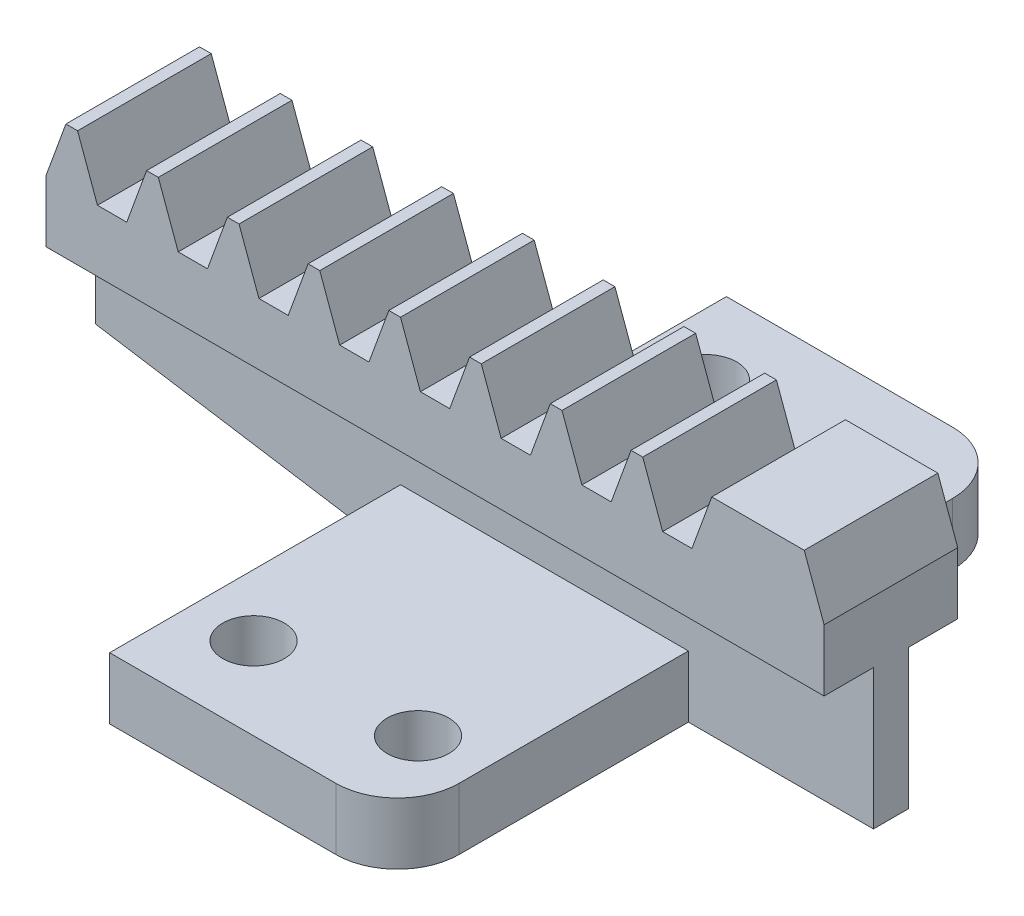
SolidWorks part; units mm, degrees
material "ABS"
ref_plane "Plan de face" through (0, 0, 0) normal (0, 0, 1) x (1, 0, 0)
ref_plane "Plan de dessus" through (0, 0, 0) normal (0, 1, 0) x (1, 0, 0)
ref_plane "Plan de droite" through (0, 0, 0) normal (1, 0, 0) x (0, 0, -1)
sketch "Esquisse1" plane through (0, 0, 0) normal (0, 0, 1) x (1, 0, 0)
  circle A1 centre (0, 0) radius 2.5
  arc A192 (-2.7975, 7.3493) -> (-3.2186, 7.1749) centre (0, 0) ccw
  arc A193 (-3.7466, 7.3576) -> (-3.2186, 7.1749) centre (-3.3855, 7.5469) ccw
  arc A194 (-3.7466, 7.3576) -> (-5.4988, 8.9274) centre (-6.7243, 5.7967) ccw
  arc A195 (-5.4988, 8.9274) -> (-6.1435, 8.4966) centre (0, 0) ccw
  arc A196 (-6.1435, 8.4966) -> (-5.3638, 6.2771) centre (-2.7822, 8.4307) ccw
  arc A197 (-5.397, 5.7193) -> (-5.3638, 6.2771) centre (-5.6769, 6.0159) ccw
  arc A198 (-5.397, 5.7193) -> (-5.7193, 5.397) centre (0, 0) ccw
  arc A199 (-6.2771, 5.3638) -> (-5.7193, 5.397) centre (-6.0159, 5.6769) ccw
  arc A200 (-6.2771, 5.3638) -> (-8.4966, 6.1435) centre (-8.4307, 2.7822) ccw
  arc A201 (-8.4966, 6.1435) -> (-8.9274, 5.4988) centre (0, 0) ccw
  arc A202 (-8.9274, 5.4988) -> (-7.3576, 3.7466) centre (-5.7967, 6.7243) ccw
  arc A203 (-7.1749, 3.2186) -> (-7.3576, 3.7466) centre (-7.5469, 3.3855) ccw
  arc A204 (-7.1749, 3.2186) -> (-7.3493, 2.7975) centre (0, 0) ccw
  arc A205 (-7.8519, 2.5534) -> (-7.3493, 2.7975) centre (-7.7304, 2.9426) ccw
  arc A206 (-7.8519, 2.5534) -> (-10.2009, 2.4244) centre (-8.8537, -0.6559) ccw
  arc A207 (-10.2009, 2.4244) -> (-10.3521, 1.6639) centre (0, 0) ccw
  arc A208 (-10.3521, 1.6639) -> (-8.2313, 0.6458) centre (-7.9287, 3.9941) ccw
  arc A209 (-7.8604, 0.2279) -> (-8.2313, 0.6458) centre (-8.268, 0.2397) ccw
  arc A210 (-7.8604, 0.2279) -> (-7.8604, -0.2279) centre (0, 0) ccw
  arc A211 (-8.2313, -0.6458) -> (-7.8604, -0.2279) centre (-8.268, -0.2397) ccw
  arc A212 (-8.2313, -0.6458) -> (-10.3521, -1.6639) centre (-7.9287, -3.9941) ccw
  arc A213 (-10.3521, -1.6639) -> (-10.2009, -2.4244) centre (0, 0) ccw
  arc A214 (-10.2009, -2.4244) -> (-7.8519, -2.5534) centre (-8.8537, 0.6559) ccw
  arc A215 (-7.3493, -2.7975) -> (-7.8519, -2.5534) centre (-7.7304, -2.9426) ccw
  arc A216 (-7.3493, -2.7975) -> (-7.1749, -3.2186) centre (0, 0) ccw
  arc A217 (-7.3576, -3.7466) -> (-7.1749, -3.2186) centre (-7.5469, -3.3855) ccw
  arc A218 (-7.3576, -3.7466) -> (-8.9274, -5.4988) centre (-5.7967, -6.7243) ccw
  arc A219 (-8.9274, -5.4988) -> (-8.4966, -6.1435) centre (0, 0) ccw
  arc A220 (-8.4966, -6.1435) -> (-6.2771, -5.3638) centre (-8.4307, -2.7822) ccw
  arc A221 (-5.7193, -5.397) -> (-6.2771, -5.3638) centre (-6.0159, -5.6769) ccw
  arc A222 (-5.7193, -5.397) -> (-5.397, -5.7193) centre (0, 0) ccw
  arc A223 (-5.3638, -6.2771) -> (-5.397, -5.7193) centre (-5.6769, -6.0159) ccw
  arc A224 (-5.3638, -6.2771) -> (-6.1435, -8.4966) centre (-2.7822, -8.4307) ccw
  arc A225 (-6.1435, -8.4966) -> (-5.4988, -8.9274) centre (0, 0) ccw
  arc A226 (-5.4988, -8.9274) -> (-3.7466, -7.3576) centre (-6.7243, -5.7967) ccw
  arc A227 (-3.2186, -7.1749) -> (-3.7466, -7.3576) centre (-3.3855, -7.5469) ccw
  arc A228 (-3.2186, -7.1749) -> (-2.7975, -7.3493) centre (0, 0) ccw
  arc A229 (-2.5534, -7.8519) -> (-2.7975, -7.3493) centre (-2.9426, -7.7304) ccw
  arc A230 (-2.5534, -7.8519) -> (-2.4244, -10.2009) centre (0.6559, -8.8537) ccw
  arc A231 (-2.4244, -10.2009) -> (-1.6639, -10.3521) centre (0, 0) ccw
  arc A232 (-1.6639, -10.3521) -> (-0.6458, -8.2313) centre (-3.9941, -7.9287) ccw
  arc A233 (-0.2279, -7.8604) -> (-0.6458, -8.2313) centre (-0.2397, -8.268) ccw
  arc A234 (-0.2279, -7.8604) -> (0.2279, -7.8604) centre (0, 0) ccw
  arc A235 (0.6458, -8.2313) -> (0.2279, -7.8604) centre (0.2397, -8.268) ccw
  arc A236 (0.6458, -8.2313) -> (1.6639, -10.3521) centre (3.9941, -7.9287) ccw
  arc A237 (1.6639, -10.3521) -> (2.4244, -10.2009) centre (0, 0) ccw
  arc A238 (2.4244, -10.2009) -> (2.5534, -7.8519) centre (-0.6559, -8.8537) ccw
  arc A239 (2.7975, -7.3493) -> (2.5534, -7.8519) centre (2.9426, -7.7304) ccw
  arc A240 (2.7975, -7.3493) -> (3.2186, -7.1749) centre (0, 0) ccw
  arc A241 (3.7466, -7.3576) -> (3.2186, -7.1749) centre (3.3855, -7.5469) ccw
  arc A242 (3.7466, -7.3576) -> (5.4988, -8.9274) centre (6.7243, -5.7967) ccw
  arc A243 (5.4988, -8.9274) -> (6.1435, -8.4966) centre (0, 0) ccw
  arc A244 (6.1435, -8.4966) -> (5.3638, -6.2771) centre (2.7822, -8.4307) ccw
  arc A245 (5.397, -5.7193) -> (5.3638, -6.2771) centre (5.6769, -6.0159) ccw
  arc A246 (5.397, -5.7193) -> (5.7193, -5.397) centre (0, 0) ccw
  arc A247 (6.2771, -5.3638) -> (5.7193, -5.397) centre (6.0159, -5.6769) ccw
  arc A248 (6.2771, -5.3638) -> (8.4966, -6.1435) centre (8.4307, -2.7822) ccw
  arc A249 (8.4966, -6.1435) -> (8.9274, -5.4988) centre (0, 0) ccw
  arc A250 (8.9274, -5.4988) -> (7.3576, -3.7466) centre (5.7967, -6.7243) ccw
  arc A251 (7.1749, -3.2186) -> (7.3576, -3.7466) centre (7.5469, -3.3855) ccw
  arc A252 (7.1749, -3.2186) -> (7.3493, -2.7975) centre (0, 0) ccw
  arc A253 (7.8519, -2.5534) -> (7.3493, -2.7975) centre (7.7304, -2.9426) ccw
  arc A254 (7.8519, -2.5534) -> (10.2009, -2.4244) centre (8.8537, 0.6559) ccw
  arc A255 (10.2009, -2.4244) -> (10.3521, -1.6639) centre (0, 0) ccw
  arc A256 (10.3521, -1.6639) -> (8.2313, -0.6458) centre (7.9287, -3.9941) ccw
  arc A257 (7.8604, -0.2279) -> (8.2313, -0.6458) centre (8.268, -0.2397) ccw
  arc A258 (7.8604, -0.2279) -> (7.8604, 0.2279) centre (0, 0) ccw
  arc A259 (8.2313, 0.6458) -> (7.8604, 0.2279) centre (8.268, 0.2397) ccw
  arc A260 (8.2313, 0.6458) -> (10.3521, 1.6639) centre (7.9287, 3.9941) ccw
  arc A261 (10.3521, 1.6639) -> (10.2009, 2.4244) centre (0, 0) ccw
  arc A262 (10.2009, 2.4244) -> (7.8519, 2.5534) centre (8.8537, -0.6559) ccw
  arc A263 (7.3493, 2.7975) -> (7.8519, 2.5534) centre (7.7304, 2.9426) ccw
  arc A264 (7.3493, 2.7975) -> (7.1749, 3.2186) centre (0, 0) ccw
  arc A265 (7.3576, 3.7466) -> (7.1749, 3.2186) centre (7.5469, 3.3855) ccw
  arc A266 (7.3576, 3.7466) -> (8.9274, 5.4988) centre (5.7967, 6.7243) ccw
  arc A267 (8.9274, 5.4988) -> (8.4966, 6.1435) centre (0, 0) ccw
  arc A268 (8.4966, 6.1435) -> (6.2771, 5.3638) centre (8.4307, 2.7822) ccw
  arc A269 (5.7193, 5.397) -> (6.2771, 5.3638) centre (6.0159, 5.6769) ccw
  arc A270 (5.7193, 5.397) -> (5.397, 5.7193) centre (0, 0) ccw
  arc A271 (5.3638, 6.2771) -> (5.397, 5.7193) centre (5.6769, 6.0159) ccw
  arc A272 (5.3638, 6.2771) -> (6.1435, 8.4966) centre (2.7822, 8.4307) ccw
  arc A273 (6.1435, 8.4966) -> (5.4988, 8.9274) centre (0, 0) ccw
  arc A274 (5.4988, 8.9274) -> (3.7466, 7.3576) centre (6.7243, 5.7967) ccw
  arc A275 (3.2186, 7.1749) -> (3.7466, 7.3576) centre (3.3855, 7.5469) ccw
  arc A276 (3.2186, 7.1749) -> (2.7975, 7.3493) centre (0, 0) ccw
  arc A277 (2.5534, 7.8519) -> (2.7975, 7.3493) centre (2.9426, 7.7304) ccw
  arc A278 (2.5534, 7.8519) -> (2.4244, 10.2009) centre (-0.6559, 8.8537) ccw
  arc A279 (2.4244, 10.2009) -> (1.6639, 10.3521) centre (0, 0) ccw
  arc A280 (1.6639, 10.3521) -> (0.6458, 8.2313) centre (3.9941, 7.9287) ccw
  arc A281 (0.2279, 7.8604) -> (0.6458, 8.2313) centre (0.2397, 8.268) ccw
  arc A282 (0.2279, 7.8604) -> (-0.2279, 7.8604) centre (0, 0) ccw
  arc A283 (-0.6458, 8.2313) -> (-0.2279, 7.8604) centre (-0.2397, 8.268) ccw
  arc A284 (-0.6458, 8.2313) -> (-1.6639, 10.3521) centre (-3.9941, 7.9287) ccw
  arc A285 (-1.6639, 10.3521) -> (-2.4244, 10.2009) centre (0, 0) ccw
  arc A286 (-2.4244, 10.2009) -> (-2.5534, 7.8519) centre (0.6559, 8.8537) ccw
  arc A287 (-2.7975, 7.3493) -> (-2.5534, 7.8519) centre (-2.9426, 7.7304) ccw
  point P3 (0, -7.8638)
extrude "Boss.-Extru.1" add sketch "Esquisse1" along normal blind 1
sketch "Esquisse2" plane through (0, 0, 1) normal (0, 0, 1) x (1, 0, 0)
  line L0 (0, 0) -> (0, -9.25) construction
  line L1 (-0.114, -9.25) -> (-13.3501, -9.25) construction
  line L2 (-0.015, -9.2555) -> (3.6062, -7.9375) construction
  line L3 (0.2847, -8) -> (1.2514, -10.656)
  line L4 (-0.2847, -8) -> (-1.2514, -10.656)
  line L5 (-0.2847, -8) -> (0.2847, -8)
  line L6 (1.2514, -10.656) -> (2.6755, -10.656)
  line L7 (3.6422, -8) -> (2.6755, -10.656)
  line L8 (3.6422, -8) -> (4.2115, -8)
  line L9 (4.2115, -8) -> (5.1782, -10.656)
  line L10 (5.1782, -10.656) -> (6.6024, -10.656)
  line L11 (7.5691, -8) -> (6.6024, -10.656)
  line L12 (7.5691, -8) -> (8.1384, -8)
  line L13 (8.1384, -8) -> (9.1051, -10.656)
  line L14 (9.1051, -10.656) -> (10.5293, -10.656)
  line L15 (11.496, -8) -> (10.5293, -10.656)
  line L16 (11.496, -8) -> (12.0653, -8)
  line L17 (12.0653, -8) -> (13.032, -10.656)
  line L18 (13.032, -10.656) -> (14.4561, -10.656)
  line L19 (15.4228, -8) -> (14.4561, -10.656)
  line L20 (15.4228, -8) -> (15.9922, -8)
  line L21 (15.9922, -8) -> (16.9589, -10.656)
  line L22 (16.9589, -10.656) -> (18.383, -10.656)
  line L23 (19.3497, -8) -> (18.383, -10.656)
  line L24 (19.3497, -8) -> (19.919, -8)
  line L25 (19.919, -8) -> (20.8857, -10.656)
  line L26 (20.8857, -10.656) -> (22.3099, -10.656)
  line L27 (23.2766, -8) -> (22.3099, -10.656)
  line L28 (23.2766, -8) -> (23.8459, -8)
  line L29 (23.8459, -8) -> (24.8126, -10.656)
  line L30 (24.8126, -10.656) -> (26.2368, -10.656)
  line L31 (27.2035, -8) -> (26.2368, -10.656)
  line L32 (27.2035, -8) -> (27.7728, -8)
  line L33 (27.7728, -8) -> (28.7395, -10.656)
  line L34 (28.7395, -10.656) -> (30.1636, -10.656)
  line L35 (31.1303, -8) -> (30.1636, -10.656)
  line L36 (31.1303, -8) -> (31.6997, -8)
  line L37 (31.6997, -8) -> (32.6664, -10.656)
  line L38 (32.6664, -10.656) -> (34.0905, -10.656)
  line L39 (35.0572, -8) -> (34.0905, -10.656)
  line L40 (35.0572, -8) -> (35.6265, -8)
  line L41 (35.6265, -8) -> (36.5932, -10.656)
  line L42 (36.5932, -10.656) -> (38.0174, -10.656) construction
  line L43 (-1.2514, -10.656) -> (-1.2514, -13.656)
  line L44 (-1.2514, -13.656) -> (36.5932, -13.656)
  line L45 (36.5932, -13.656) -> (36.5932, -10.656)
  circle A0 centre (0, 0) radius 9.25 construction
  circle A1 centre (0, -9.25) radius 0.845 construction
  circle A2 centre (0, -9.25) radius 0.695 construction
  arc A3 (-1.6639, -10.3521) -> (-0.6458, -8.2313) centre (-3.9941, -7.9287) ccw construction
  point P8 (0, -9.25)
  dimension "D1" = 18.5
  dimension "D3" = 0.15
  dimension "D2" = 20
  dimension "D4" = 1.25
  dimension "D5" = 1.406
  dimension "D6" = 10
  dimension "D7" = 3.9269
  dimension "D8" = 3
extrude "Boss.-Extru.2" add sketch "Esquisse2" along normal blind 6.5
sketch "Esquisse3" plane through (0, 0, 0) normal (0, 0, -1) x (-1, 0, 0)
  circle A0 centre (0, 0) radius 14.1374
extrude "Enlèv. mat.-Extru.1" cut sketch "Esquisse3" against normal up to surface (1 mm away) up to face at (17.3577, -9.4996, 1)
sketch "Esquisse4" plane through (0, -13.656, 0) normal (0, -1, 0) x (1, 0, 0)
  line L0 (-1.2514, 7.5) -> (-1.2514, 1) construction
  line L1 (-1.2514, 5.1) -> (36.5932, 5.1)
  line L2 (-1.2514, 5.1) -> (-1.2514, 3.4)
  line L3 (-1.2514, 3.4) -> (36.5932, 3.4)
  line L4 (36.5932, 5.1) -> (36.5932, 3.4)
  line L5 (36.5932, 7.5) -> (36.5932, 1) construction
  point P8 (-1.2514, 4.25)
  dimension "D1" = 1.7
extrude "Boss.-Extru.3" add sketch "Esquisse4" along normal blind 3.8 contours L2 L1 L4 L3
sketch "Esquisse5" plane through (0, 0, 0) normal (0, 1, 0) x (1, 0, 0)
  line L0 (-1.2514, -1) -> (36.5932, -7.5) construction
  line L1 (-1.2514, -1) -> (36.5932, -1) construction
  line L2 (-1.2514, -1) -> (-1.2514, -7.5) construction
  line L3 (-1.2514, -7.5) -> (36.5932, -7.5) construction
  line L4 (36.5932, -1) -> (36.5932, -7.5) construction
  line L5 (17.6709, -4.25) -> (26.5932, -4.25) construction
  line L11 (16.5932, 10.75) -> (36.5932, 10.75)
  line L12 (16.5932, 10.75) -> (16.5932, -19.25)
  line L13 (16.5932, -19.25) -> (36.5932, -19.25)
  line L14 (36.5932, 10.75) -> (36.5932, -19.25)
  line L15 (16.5932, 10.75) -> (36.5932, -19.25) construction
  line L16 (16.5932, -19.25) -> (36.5932, 10.75) construction
  point P6 (17.6709, -4.25)
  dimension "D1" = 30
  dimension "D2" = 20
extrude "Boss.-Extru.4" add sketch "Esquisse5" against normal blind 3 from surface starting at face at (17.6709, -17.456, 4.25)
sketch "Esquisse7" plane through (0, 0, 0) normal (0, 1, 0) x (1, 0, 0)
  line L0 (16.5932, -19.25) -> (36.5932, -19.25) construction
  line L1 (16.5932, 10.75) -> (13.5932, 10.75)
  line L2 (16.5932, 10.75) -> (16.5932, -19.25)
  line L3 (16.5932, -19.25) -> (13.5932, -19.25)
  line L4 (13.5932, 10.75) -> (13.5932, -19.25)
  dimension "D1" = 3
extrude "Boss.-Extru.5" add sketch "Esquisse7" against normal blind 3 from surface starting at face at (26.5932, -17.456, 12.175)
chamfer "Chanfrein1" distance 3 angle 81 1 edges at (13.5932, -17.456, 4.25) first distance on face at (13.5932, -18.456, 4.25)
sketch "Esquisse6" plane through (0, 0, 0) normal (0, 1, 0) x (1, 0, 0)
  line L0 (20.8857, -4.25) -> (19.919, -4.25) construction
  line L1 (36.5932, 10.75) -> (13.5932, 10.75) construction
  line L6 (16.5932, -15.25) -> (24.5932, -15.25) construction
  line L9 (16.5932, -15.25) -> (16.5932, 6.75) construction
  line L10 (16.5932, 6.75) -> (24.5932, 6.75) construction
  line L11 (24.5932, -15.25) -> (24.5932, 6.75) construction
  line L12 (16.5932, -15.25) -> (24.5932, 6.75) construction
  line L13 (16.5932, 6.75) -> (24.5932, -15.25) construction
  line L17 (20.8857, -7.5) -> (20.8857, -1) construction
  line L18 (19.919, -7.5) -> (19.919, -1) construction
  line L19 (13.5932, -5.1) -> (13.5932, -19.25) construction
  circle A4 centre (16.5932, 6.75) radius 1.5
  circle A5 centre (24.5932, 6.75) radius 1.5
  circle A6 centre (24.5932, -15.25) radius 1.5
  circle A7 centre (16.5932, -15.25) radius 1.5
  point P4 (20.5932, -4.25)
  point P11 (20.5932, -4.25)
  dimension "D3" = 3
  dimension "D4" = 8
  dimension "D1" = 4
  dimension "D2" = 3
extrude "Enlèv. mat.-Extru.2" cut sketch "Esquisse6" against normal through all
sketch "Esquisse8" plane through (0, 0, 0) normal (0, 0, 1) x (1, 0, 0)
  line L0 (31.6997, -8) -> (35.0572, -8)
  line L1 (35.0572, -8) -> (34.0905, -10.656)
  line L2 (34.0905, -10.656) -> (32.6664, -10.656)
  line L3 (32.6664, -10.656) -> (31.6997, -8)
extrude "Boss.-Extru.6" add sketch "Esquisse8" along normal up to surface (7.5 mm away) from surface up to face at (17.6709, -9.5341, 7.5) starting at face at (17.6709, -9.5341, 1)
sketch "Esquisse9" plane through (0, -17.456, 0) normal (0, 1, 0) x (1, 0, 0)
  line L0 (13.5932, -19.25) -> (36.5932, -19.25) construction
  line L1 (36.5932, 10.75) -> (27.5932, 10.75)
  line L2 (36.5932, 10.75) -> (36.5932, -3.4)
  line L3 (36.5932, -19.25) -> (27.5932, -19.25)
  line L4 (27.5932, 10.75) -> (27.5932, -3.4)
  line L5 (36.5932, -5.1) -> (36.5932, -3.4) construction
  line L6 (36.5932, -3.4) -> (27.5932, -3.4)
  line L7 (27.5932, -3.4) -> (27.5932, -5.1) construction
  line L8 (27.5932, -5.1) -> (36.5932, -5.1)
  line L9 (27.5932, -3.4) -> (27.5932, -5.1) construction
  line L10 (27.5932, -5.1) -> (27.5932, -19.25)
  line L11 (36.5932, -3.4) -> (36.5932, -5.1) construction
  line L12 (36.5932, -5.1) -> (36.5932, -19.25)
  circle A0 centre (24.5932, -15.25) radius 1.5 construction
  dimension "D1" = 3
extrude "Enlèv. mat.-Extru.3" cut sketch "Esquisse9" against normal through all
fillet "Congé2" radius 3 2 edges at (27.5932, -18.956, 19.25) (27.5932, -18.956, -10.75)
